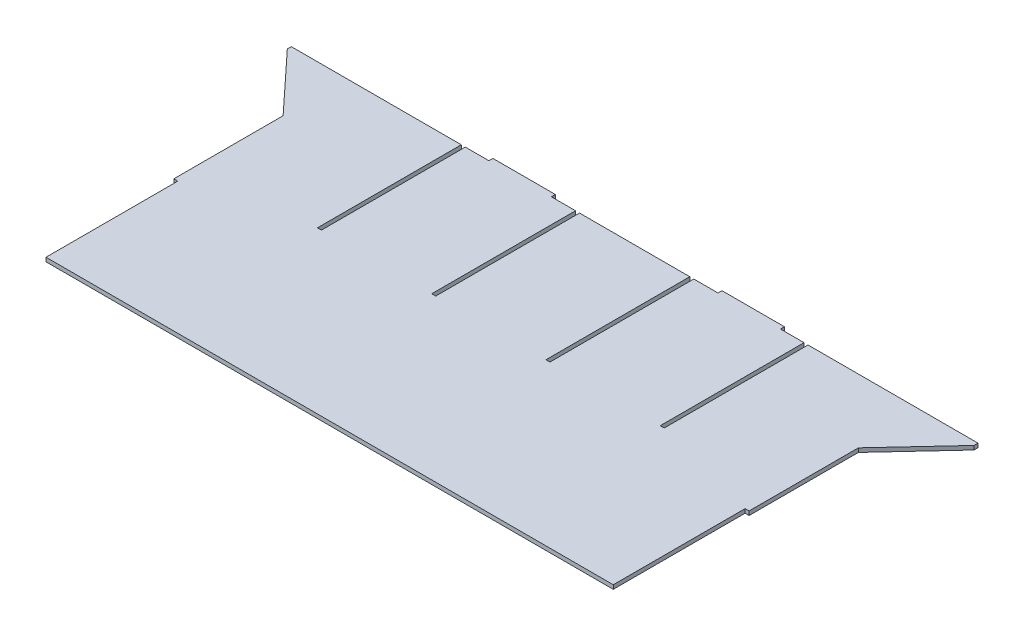
SolidWorks part; units mm, degrees
material "6061-T6 (SS)"
ref_plane "X-Y Datum" through (0, 0, 0) normal (0, 0, 1) x (1, 0, 0)
ref_plane "X-Z Datum" through (0, 0, 0) normal (0, 1, 0) x (1, 0, 0)
ref_plane "Y-Z Datum" through (0, 0, 0) normal (1, 0, 0) x (0, 0, -1)
sketch "Sketch1" plane through (0, 0, 0) normal (0, 0, 1) x (1, 0, 0)
  line L1 (-228.601, -1.5875) -> (228.601, -1.5875)
  line L2 (-228.601, -1.5875) -> (-228.601, 1.5875)
  line L3 (-228.601, 1.5875) -> (228.601, 1.5875)
  line L4 (228.601, -1.5875) -> (228.601, 1.5875)
  line L5 (-228.601, -1.5875) -> (228.601, 1.5875) construction
  line L6 (-228.601, 1.5875) -> (228.601, -1.5875) construction
  point P0 (0, 0)
  dimension "D1" = 3.175
  dimension "D2" = 457.202
extrude "Boss-Extrude1" add sketch "Sketch1" along normal blind 242.425
sketch "Sketch2" plane through (0, 1.5875, 0) normal (0, 1, 0) x (1, 0, 0)
  line L0 (228.601, 0) -> (225.426, 0)
  line L1 (228.601, 0) -> (-228.601, 0) construction
  line L2 (225.426, 0) -> (137.796, 0)
  line L3 (137.796, 0) -> (134.621, 0)
  line L10 (134.621, 0) -> (137.796, 0)
  line L11 (134.621, 0) -> (134.621, -114.3)
  line L12 (134.621, -114.3) -> (137.796, -114.3)
  line L13 (137.796, 0) -> (137.796, -114.3)
  line M2 (228.601, 0) -> (-228.601, 0)
  dimension "D1" = 87.63
  dimension "D2" = 3.175
  dimension "D3" = 114.3
  dimension "D4" = 3.175
extrude "Cut-Extrude1" cut sketch "Sketch2" against normal through all contours L13 L11 L12 M2 region at (136.2085, 1.5875, 57.15)
pattern_linear "LPattern1" count 4 spacing 90.807 along (-1, 0, 0) of "Cut-Extrude1"
sketch "Sketch3" plane through (0, 0, 0) normal (0, 0, -1) x (-1, 0, 0)
  line L1 (-115.8495, 1.5875) -> (-66.1907, 1.5875)
  line L2 (-115.8495, 1.5875) -> (-115.8495, -1.5875)
  line L3 (-115.8495, -1.5875) -> (-66.1907, -1.5875)
  line L4 (-66.1907, 1.5875) -> (-66.1907, -1.5875)
  line L5 (66.1907, 1.5875) -> (115.8495, 1.5875)
  line L6 (66.1907, 1.5875) -> (66.1907, -1.5875)
  line L7 (66.1907, -1.5875) -> (115.8495, -1.5875)
  line L8 (115.8495, 1.5875) -> (115.8495, -1.5875)
extrude "Boss-Extrude2" add sketch "Sketch3" along normal blind 3.175
sketch "Sketch4" plane through (0, -1.5875, 0) normal (0, -1, 0) x (1, 0, 0)
  line L0 (-228.601, 0) -> (-272.876, 0)
  line L2 (-228.601, 242.425) -> (-228.601, 0) construction
  line L3 (-228.601, 50.8) -> (-228.601, 0)
  line L4 (-272.876, 0) -> (-272.876, 3.175)
  line L5 (-272.876, 3.175) -> (-228.601, 50.8)
  dimension "D1" = 44.275
  dimension "D2" = 50.8
  dimension "D3" = 3.175
extrude "Boss-Extrude3" add sketch "Sketch4" against normal blind 3.175
mirror "Mirror1" about plane through (0, 0, 0) normal (1, 0, 0) of "Boss-Extrude3"
sketch "Sketch5" plane through (0, -1.5875, 0) normal (0, -1, 0) x (1, 0, 0)
  line L1 (-228.601, 242.425) -> (-225.426, 242.425)
  line L2 (-228.601, 242.425) -> (-228.601, 137.65)
  line L3 (-228.601, 137.65) -> (-225.426, 137.65)
  line L4 (-225.426, 242.425) -> (-225.426, 137.65)
  dimension "D1" = 3.175
  dimension "D2" = 104.775
extrude "Cut-Extrude2" cut sketch "Sketch5" against normal blind 3.175
mirror "Mirror2" about plane through (0, 0, 0) normal (1, 0, 0) of "Cut-Extrude2"
